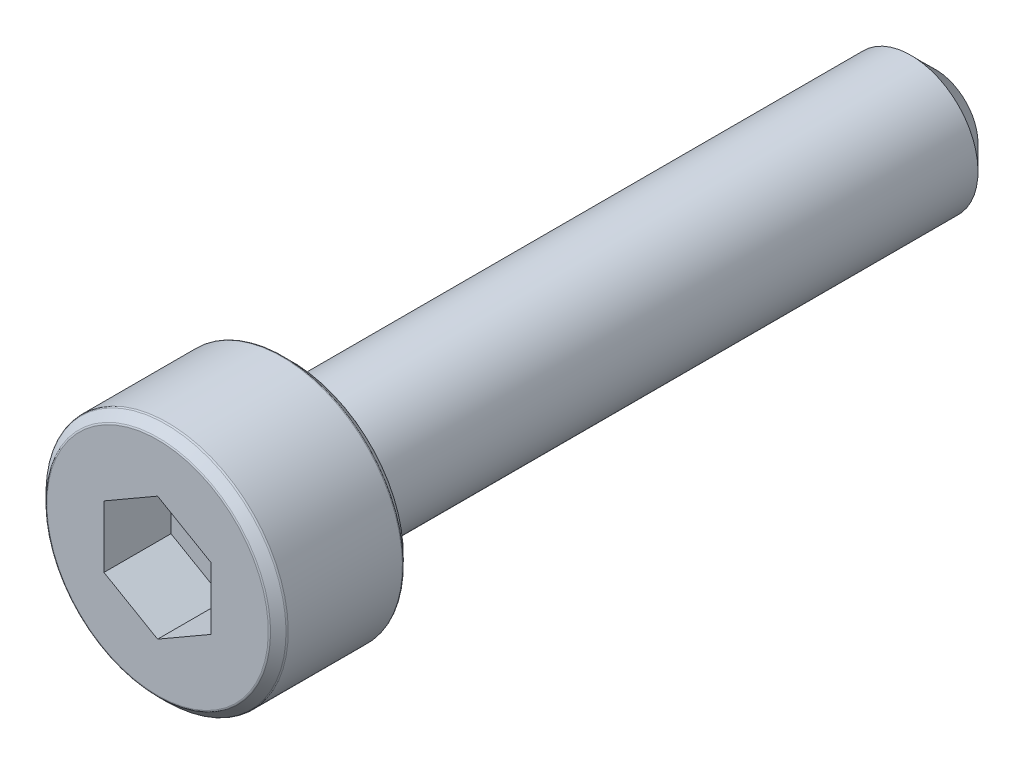
SolidWorks part; units mm, degrees
ref_plane "Front Plane" through (0, 0, 0) normal (0, 0, 1) x (1, 0, 0)
ref_plane "Top Plane" through (0, 0, 0) normal (0, 1, 0) x (1, 0, 0)
ref_plane "Right Plane" through (0, 0, 0) normal (1, 0, 0) x (0, 0, -1)
other "Configuration Table"
sketch "Sketch1" plane through (0, 0, 0) normal (1, 0, 0) x (0, 0, -1)
  line L0 (-7.25, 0) -> (7.25, 0) construction
  line L1 (-7.25, 0) -> (-7.25, 2.25)
  line L2 (-7.25, 2.25) -> (-4.75, 2.25)
  line L3 (-4.75, 2.25) -> (-4.75, 1.25)
  line L4 (-4.75, 1.25) -> (6.7953, 1.25)
  line L5 (7.2062, 1.3258) -> (7.5562, 0.7196) construction
  line L6 (7.5562, 0.7196) -> (7.9062, 1.3258) construction
  line L7 (7.9062, 1.3258) -> (7.2062, 1.3258) construction
  line L8 (6.7953, 1.25) -> (7.25, 0.7953)
  line L9 (7.25, 0.7953) -> (7.25, 0)
  line L10 (7.25, 1.25) -> (7.8625, 1.25) construction
  line L11 (7.5562, 1.3258) -> (7.5562, 1.25) construction
  line L12 (7.5562, 1.25) -> (7.5562, 0.7953) construction
  line L13 (7.5562, 0.7953) -> (7.5562, 0.7196) construction
  line L14 (7.5125, 0.7953) -> (7.6, 0.7953)
  line L15 (7.2281, 1.2879) -> (7.8844, 1.2879)
  line L16 (7.6, 0.7953) -> (7.8844, 1.2879)
  line L17 (7.5125, 0.7953) -> (7.2281, 1.2879)
  line L18 (-7.25, 1) -> (-6, 1)
  line L19 (-6, 1) -> (-6, 0)
  line L20 (4.8, 1.25) -> (4.8, -1.25) construction
  point P20 (7.5562, 1.2879)
  point P22 (4.8, -1.25)
  point P28 (4.8, 0)
  point P29 (6.7953, -1.25)
  dimension "Head Diameter" = 4.5
  dimension "Head Height" = 2.5
  dimension "Thread Size" = 2.5
  dimension "D1" = 45
  dimension "Thread Pitch" = 0.7
  dimension "D3" = 0.0875
  dimension "Drive Size" = 2
  dimension "D4" = 2.45
  dimension "D5" = 1.25
sketch "Sketch3" plane through (0, 0, 0) normal (1, 0, 0) x (0, 0, -1)
  line L0 (-7.25, 2.0638) -> (-7.25, 1)
  line L1 (-7.25, 1) -> (-6, 1)
  line L2 (-6, 1) -> (-6, 0)
  line L3 (-6, 0) -> (7.25, 0)
  line L4 (7.25, 0) -> (7.25, 0.7953)
  line L5 (7.25, 0.7953) -> (6.7953, 1.25)
  line L6 (6.7953, 1.25) -> (-4.75, 1.25)
  line L7 (-4.75, 1.25) -> (-4.75, 2.0638)
  line L8 (-4.9362, 2.25) -> (-7.0638, 2.25)
  line L9 (-7.2376, 2.0936) -> (-7.0936, 2.2376)
  line L11 (-7.25, 2.25) -> (-4.75, 2.25) construction
  line L12 (-4.9064, 2.2376) -> (-4.7624, 2.0936)
  arc A5 (-4.7624, 2.0936) -> (-4.75, 2.0638) centre (-4.7922, 2.0638) cw
  arc A6 (-4.9362, 2.25) -> (-4.9064, 2.2376) centre (-4.9362, 2.2078) cw
  arc A7 (-7.0638, 2.25) -> (-7.0936, 2.2376) centre (-7.0638, 2.2078) ccw
  arc A8 (-7.25, 2.0638) -> (-7.2376, 2.0936) centre (-7.2078, 2.0638) cw
  point P17 (-6, 2.25)
  point P29 (-7.25, 2.0813)
  dimension "D3" = 0.0422
  dimension "D1" = 45
  dimension "D2" = 0.1687
revolve "Revolve1" add sketch "Sketch3" angle 360 about L0
sketch "Sketch4" plane through (0, 0, 7.25) normal (0, 0, 1) x (1, 0, 0)
  line L1 (0, 1.1547) -> (-1, 0.5774)
  line L2 (-1, 0.5774) -> (-1, -0.5774)
  line L3 (-1, -0.5774) -> (0, -1.1547)
  line L4 (0, -1.1547) -> (1, -0.5774)
  line L5 (1, -0.5774) -> (1, 0.5774)
  line L6 (1, 0.5774) -> (0, 1.1547)
  circle A0 centre (0, 0) radius 1 construction
extrude "Cut-Extrude1" cut sketch "Sketch4" against normal up to vertex (1.25 mm away) up to point (0, 1, 6)
sketch "Sketch5" plane through (0, 0, 7.25) normal (0, 0, 1) x (1, 0, 0)
  circle A0 centre (0, 0) radius 1.1547
extrude "Cut-Extrude2" [suppressed] cut sketch "Sketch5" against normal up to next draft 45
sketch "Sketch10" [suppressed] plane through (0, 0, 22.5) normal (0, 0, 1) x (1, 0, 0)
  line L0 (1.5, 0.866) -> (1.5, -0.866) construction
  circle A0 centre (0, 0) radius 1.5
extrude "Cut-Extrude3" [suppressed] cut sketch "Sketch10" against normal through all draft 60
fillet "Fillet1" [suppressed] radius 0.1
sketch "Sketch6" [suppressed] plane through (0, 0, -24.5) normal (0, 0, -1) x (-1, 0, 0)
  circle A0 centre (0, 0) radius 2 construction
  circle A1 centre (0, 0) radius 2
curve "Helix/Spiral1" [suppressed]
sketch "Sketch7" [suppressed] plane through (0, 0, 0) normal (1, 0, 0) x (0, 0, -1)
  line L0 (24.7625, 1.5453) -> (24.85, 1.5453) construction
  line L1 (24.7625, 1.5453) -> (24.4781, 2.0379) construction
  line L2 (24.4781, 2.0379) -> (25.1344, 2.0379) construction
  line L3 (24.85, 1.5453) -> (25.1344, 2.0379) construction
  line L4 (24.7625, 1.5453) -> (24.85, 1.5453)
  line L5 (24.7625, 1.5453) -> (24.4781, 2.0379)
  line L6 (24.4781, 2.0379) -> (25.1344, 2.0379)
  line L7 (24.85, 1.5453) -> (25.1344, 2.0379)
sweep "Cut-Sweep1" [suppressed] cut profiles "Sketch7" path "Helix/Spiral1"
sketch "Sketch11" [suppressed] plane through (0, 0, 0) normal (1, 0, 0) x (0, 0, -1)
  line L0 (-20.5, 2.175) -> (-20.325, 2) construction
  line L1 (-20.5, 3.5) -> (-20.5, 2) construction
  line L2 (-20.5, 2) -> (24.0453, 2) construction
  line L3 (-20.325, 2) -> (-20.15, 2)
  line L4 (-20.15, 2) -> (-18.15, 0)
  line L5 (-24.5, 0) -> (24.5, 0) construction
  line L6 (-18.15, 0) -> (-20.5, 0)
  line L7 (-20.5, 0) -> (-20.5, 2.175) construction
  line L8 (-20.5, 2.175) -> (-21.634, 2.175)
  line L9 (-21.634, 2.175) -> (-21.634, 0)
  line L10 (-21.634, 0) -> (-20.5, 0)
  arc A0 (-20.325, 2) -> (-20.5, 2.175) centre (-20.325, 2.175) cw
  dimension "D1" = 45
  dimension "D2" = 0.175
  dimension "D3" = 45
  dimension "D4" = 0.35
revolve "Revolve2" [suppressed] add sketch "Sketch11" angle 360 about L6
equation "\"D3@Sketch1\" = \"Thread Pitch@Sketch1\" / 8"
equation "\"D4@Sketch1\" = \"Thread Pitch@Sketch1\" * 3.5"
equation "\"D3@Helix/Spiral1\" = \"Length@Sketch1\" + \"Thread Pitch@Sketch1\""
equation "\"D4@Helix/Spiral1\" = \"Thread Pitch@Sketch1\""
equation "\"D5@Sketch1\"=\"Head Height@Sketch1\"*0.5"
equation "\"D2@Sketch3\"=\"Head Diameter@Sketch1\" *0.0375"
equation "\"D2@Sketch11\"=\"Thread Pitch@Sketch1\" / 4"
equation "\"D4@Sketch11\"=\"Thread Pitch@Sketch1\"/2"
equation "\"D1@Fillet1\"=\"Drive Size@Sketch1\"*0.05"
equation "\"D1@Fillet1\" = \"Drive Size@Sketch1\" * 0.05"
equation "\"D3@Sketch3\"=\"D2@Sketch3\"*0.25"
